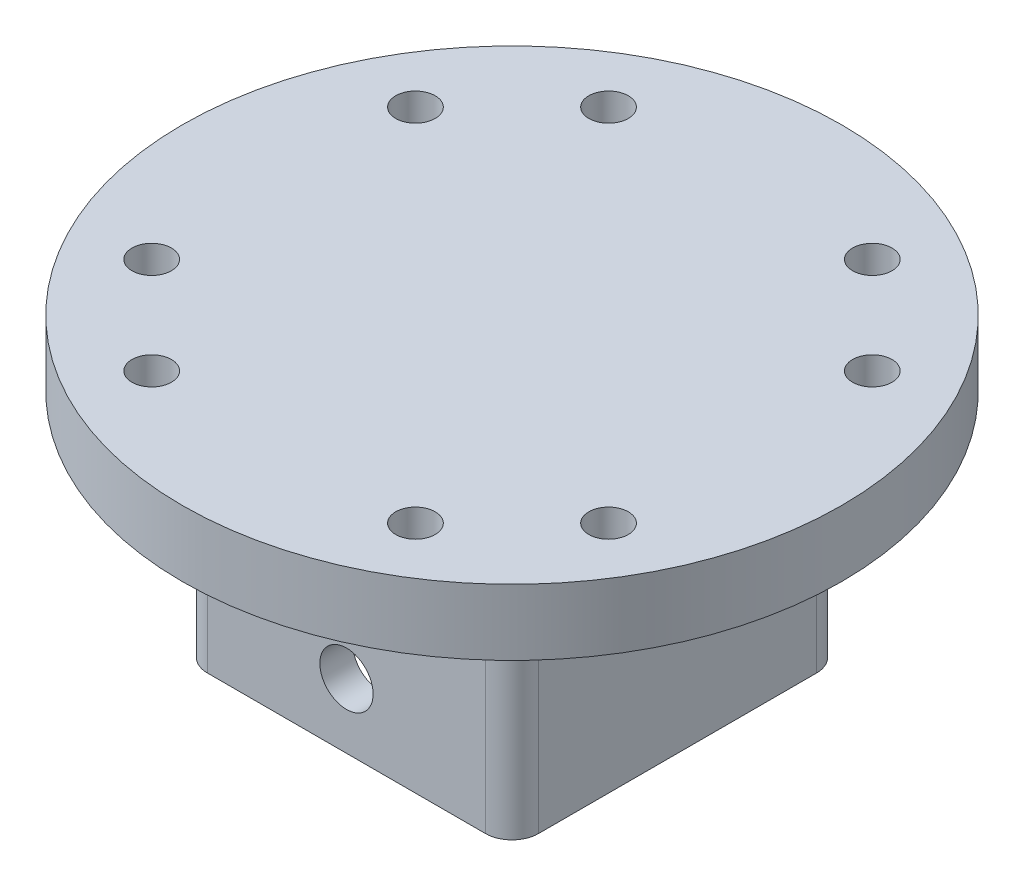
SolidWorks part; units mm, degrees
ref_plane "Front Plane" through (0, 0, 0) normal (0, 0, 1) x (1, 0, 0)
ref_plane "Top Plane" through (0, 0, 0) normal (0, 1, 0) x (1, 0, 0)
ref_plane "Right Plane" through (0, 0, 0) normal (1, 0, 0) x (0, 0, -1)
sketch "Sketch1" plane through (0, 0, 0) normal (0, 1, 0) x (1, 0, 0)
  circle A0 centre (0, 0) radius 31.75 construction
  circle A1 centre (0, 0) radius 15.9385 construction
  circle A2 centre (0, 0) radius 12.7635 construction
  dimension "D1" = 63.5
  dimension "D2" = 25.527
  dimension "D3" = 3.175
sketch "Sketch6" plane through (0, 0, 0) normal (0, 0, 1) x (1, 0, 0)
  line L0 (0, -18.7832) -> (0, 8.1093) construction
sketch "Sketch2" plane through (0, 0, 0) normal (0, 1, 0) x (1, 0, 0)
  circle A0 centre (0, 0) radius 31.75 construction
  circle A1 centre (0, 0) radius 31.75
extrude "Boss-Extrude1" add sketch "Sketch2" along normal blind 6.35
sketch "Sketch3" plane through (0, 0, 0) normal (0, 1, 0) x (1, 0, 0)
  line L0 (15.9385, 15.9385) -> (15.9385, -15.9385)
  line L1 (15.9385, -15.9385) -> (-15.9385, -15.9385)
  line L2 (-15.9385, -15.9385) -> (-15.9385, 15.9385)
  line L3 (-15.9385, 15.9385) -> (15.9385, 15.9385)
  circle A2 centre (0, 0) radius 15.9385 construction
extrude "Boss-Extrude2" add sketch "Sketch3" against normal blind 22.225
sketch "Sketch4" plane through (0, 0, 0) normal (0, 1, 0) x (1, 0, 0)
  line L0 (12.7635, 12.7635) -> (12.7635, -12.7635)
  line L1 (12.7635, -12.7635) -> (-12.7635, -12.7635)
  line L2 (-12.7635, -12.7635) -> (-12.7635, 12.7635)
  line L3 (-12.7635, 12.7635) -> (12.7635, 12.7635)
  circle A2 centre (0, 0) radius 12.7635 construction
extrude "Cut-Extrude1" cut sketch "Sketch4" against normal through all
sketch "Sketch5" plane through (0, 0, 0) normal (0, 1, 0) x (1, 0, 0)
  line L0 (0, 0) -> (37.5473, 0) construction
  line L1 (0, 0) -> (21.997, 12.7) construction
  circle A1 centre (21.997, 12.7) radius 1.9
  circle A2 centre (21.997, -12.7) radius 1.9
  dimension "D5" = 3.8
  dimension "D2" = 30
  dimension "D3" = 25.4
extrude "Cut-Extrude2" cut sketch "Sketch5" along normal through all
sketch "Sketch7" plane through (0, 0, 0) normal (0, 0, 1) x (1, 0, 0)
  line L0 (0, -18.7832) -> (0, 8.1093) construction
  circle A0 centre (0, -16.002) radius 2.5635
  dimension "D1" = 5.127
  dimension "D2" = 16.002
extrude "Cut-Extrude3" cut sketch "Sketch7" against normal through all both and the other way through all
pattern_circular "CirPattern2" count 4 over 360 about axis through (0, -18.7832, 0) along (0, 1, 0) of "Cut-Extrude2" reverse direction yes
fillet "Fillet2" radius 2.54 4 edges at (-15.9385, -11.1125, 15.9385) (15.9385, -11.1125, 15.9385) (15.9385, -11.1125, -15.9385) (-15.9385, -11.1125, -15.9385)
fillet "Fillet3" radius 2.54 8 edges at (15.1946, 0, -15.1946) (15.9385, 0, 0) (15.1946, 0, 15.1946) (0, 0, 15.9385) (-15.1946, 0, 15.1946) (-15.9385, 0, 0) (-15.1946, 0, -15.1946) (0, 0, -15.9385)
equation "\"tightTol\" = 0.005in"
equation "\"normTol\"= 0.01in"
equation "\"looseTol\"= 0.02in"
equation "\"D2@Sketch1\"=\"tightTol\"+1.000000in"
equation "\"D5@Sketch5\"=3.8mm"
equation "\"D1@Sketch7\"=\"tightTol\"+5mm"
equation "\"D2@Sketch7\"=\"tightTol\"+0.625000in"
